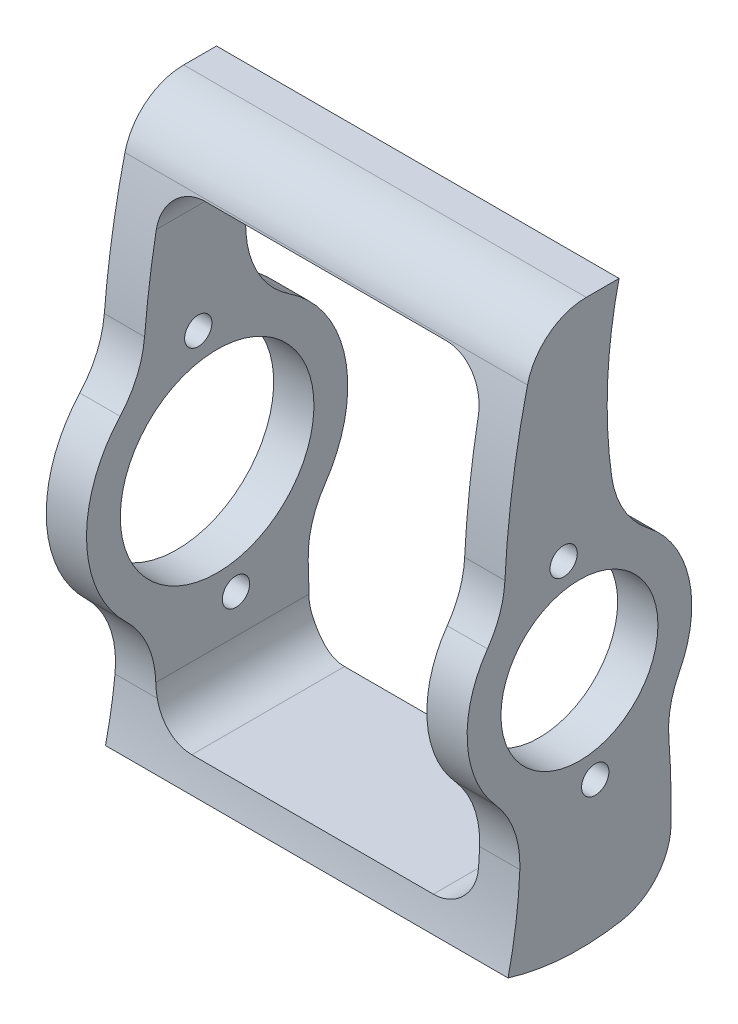
SolidWorks part; units mm, degrees
other "Markup2"
sketch "Sketch9" plane through (31.75, 50.4016, 20.35) normal (0.8402, 0.4575, 0.2911) x (0.3274, 0, -0.9449)
material "AISI 4340 Steel, normalized"
ref_plane "Front Plane" through (0, 0, 0) normal (0, 0, 1) x (1, 0, 0)
ref_plane "Top Plane" through (0, 0, 0) normal (0, 1, 0) x (1, 0, 0)
ref_plane "Right Plane" through (0, 0, 0) normal (1, 0, 0) x (0, 0, -1)
other "Center of Mass"
sketch "Weapon Layout" plane through (0, 0, 0) normal (1, 0, 0) x (0, 0, -1)
  line L0 (-6.2484, 50.4143) -> (6.2484, 50.4143) construction
  line L1 (-11.2609, -36.3978) -> (14.119, -35.3873) construction
  line L2 (6.2484, 50.4143) -> (-5.4512, 0) construction
  line L3 (6.2484, 50.4143) -> (0, 0) construction
  line L4 (0, 0) -> (0, -35.9495) construction
  circle A0 centre (0, 0) radius 14 construction
  circle A1 centre (0, 0) radius 50.8 construction
  circle A2 centre (0, 0) radius 17.175 construction
  circle A3 centre (0, 0) radius 20.35 construction
  arc A4 (-6.2484, 50.4143) -> (-20.35, 0) centre (76.8181, 0) ccw construction
  arc A5 (25.0504, -28.707) -> (-25.4024, -28.3959) centre (0, 0) cw construction
  arc A6 (6.2484, 50.4143) -> (15.4079, 13.2936) centre (47.3713, 40.8709) ccw construction
  dimension "D1" = 28
  dimension "D2" = 101.6
  dimension "D3" = 3.175
  dimension "D4" = 6.35
  dimension "D5" = 12.4968
  dimension "D7" = 6
  dimension "D6" = 12.7
  dimension "D8" = 25.4
  dimension "D9" = 87.72
sketch "Sketch2" plane through (0, 0, 0) normal (1, 0, 0) x (0, 0, -1)
  line L0 (-6.2484, 50.4143) -> (6.2484, 50.4143)
  line L1 (-11.3224, -1.5644) -> (0, 0) construction
  line L2 (6.2484, 50.4143) -> (-5.4512, 0) construction
  line L3 (-11.5831, 0.9204) -> (-15.1384, 50.4143) construction
  arc A0 (-11.2609, -36.3978) -> (14.119, -35.3873) centre (0, 0) ccw
  arc A1 (-25.4024, -28.3959) -> (25.0504, -28.707) centre (0, 0) ccw construction
  arc A2 (-10.8995, -4.0268) -> (-11.5831, 0.9204) centre (26.419, 3.6503) cw
  arc A3 (9.7624, 6.6179) -> (11.7942, -0.0229) centre (-25.5032, -7.8024) cw
  arc A4 (-11.5831, 0.9204) -> (-6.2484, 50.4143) centre (127.7924, 10.9323) cw
  arc A5 (-10.8995, -4.0268) -> (-11.2609, -36.3978) centre (-85.5365, -19.3811) cw
  arc A6 (6.2484, 50.4143) -> (9.7624, 6.6179) centre (76.8178, 34.0373) ccw
  arc A7 (11.7942, -0.0229) -> (14.119, -35.3873) centre (-112.5302, -25.9546) cw
  circle A9 centre (0, 0) radius 11.43 construction
  point P25 (10.9299, 3.3439)
  dimension "D1" = 127
  dimension "D2" = 38.1
  dimension "D3" = 76.2
  dimension "D4" = 38.1
  dimension "D5" = 22.86
  dimension "D6" = 8.89
extrude "Boss-Extrude2" add sketch "Sketch2" along normal mid plane 63.5
sketch "Sketch3" plane through (0, 0, 0) normal (0, 0, 1) x (1, 0, 0)
  line L0 (31.75, 50.4143) -> (-31.75, 50.4143) construction
  line L1 (-25.4, 42.7943) -> (25.4, 42.7943)
  line L2 (-25.4, 42.7943) -> (-25.4, -31.75)
  line L3 (-25.4, -31.75) -> (25.4, -31.75)
  line L4 (25.4, 42.7943) -> (25.4, -31.75)
  line L6 (-31.75, -38.1) -> (31.75, -38.1) construction
  line L7 (-31.75, 50.4143) -> (-31.75, 0.9204) construction
  dimension "D4" = 6.35
  dimension "D1" = 7.62
  dimension "D3" = 6.35
  dimension "D2" = 6.35
extrude "Cut-Extrude1" cut sketch "Sketch3" against normal through all both and the other way through all
fillet "Fillet1" radius 6.35 4 edges at (-25.4, 42.7943, 1.6785) (25.4, 42.7943, 1.6785) (25.4, -31.75, -1.9952) (-25.4, -31.75, -1.9952)
fillet "Fillet3" radius 9.525 2 edges at (0, -35.3873, -14.119) (0, 50.4143, 6.2484)
sketch "Sketch6" plane through (-31.75, 0, 0) normal (-1, 0, 0) x (0, 0, 1)
  circle A0 centre (0, 0) radius 20.604
  dimension "D1" = 41.208
extrude "Boss-Extrude3" add sketch "Sketch6" against normal up to surface (6.35 mm away) up to face at (-25.4, 3.1884, 0.3076)
sketch "Sketch7" plane through (-31.75, 0, 0) normal (-1, 0, 0) x (0, 0, 1)
  circle A0 centre (0, 0) radius 15.27
  arc A1 (9.3433, -18.3637) -> (11.8156, 16.8795) centre (0, 0) ccw construction
  dimension "D1" = 30.54
extrude "Cut-Extrude3" cut sketch "Sketch7" against normal up to next
sketch "Sketch10" plane through (31.75, 0, 0) normal (1, 0, 0) x (0, 0, -1)
  circle A0 centre (0, 0) radius 17.7165
  dimension "D1" = 35.433
extrude "Boss-Extrude4" add sketch "Sketch10" against normal up to surface (6.35 mm away) up to face at (25.4, 3.1884, 0.3076)
sketch "Sketch5" plane through (31.75, 0, 0) normal (1, 0, 0) x (0, 0, -1)
  circle A0 centre (0, 0) radius 12.3825
  circle A1 centre (0, 0) radius 6.35 construction
  dimension "D1" = 12.7
  dimension "D2" = 24.765
extrude "Cut-Extrude2" cut sketch "Sketch5" against normal up to next
fillet "Fillet2" radius 15.24 8 edges at (-28.575, 16.8795, 11.8156) (-28.575, -18.3637, 9.3433) (-28.575, -15.1114, -14.006) (-28.575, 19.7734, -5.7912) (28.575, 16.4667, -6.5361) (28.575, -11.3248, -13.6243) (28.575, -14.9769, 9.4639) (28.575, 13.1019, 11.9254)
sketch "Sketch11" plane through (31.75, 0, 0) normal (1, 0, 0) x (0, 0, -1)
  circle A0 centre (-2.4917, 16.1603) radius 1.8986
  circle A1 centre (-2.4917, 16.1603) radius 1.8986 construction
  circle A2 centre (2.4917, -16.1603) radius 1.8987
  circle A3 centre (2.4917, -16.1603) radius 1.8986 construction
hole_wizard "#6 Clearance Hole1" positions "Sketch12" profile "Sketch13" hole size "#6" standard "ANSI Inch"
sketch "Sketch12" plane through (-31.75, 0, 0) normal (1, 0, 0) x (0, 0, -1)
  point P0 (-2.9763, 19.3027)
  point P3 (2.9763, -19.3027)
sketch "Sketch13" plane through (-31.75, 19.3027, 2.9763) normal (0, 1, 0) x (0, 0, 1)
  line L0 (0, 0) -> (0, 8.9134)
  line L1 (0, 8.9134) -> (2.1526, 7.62)
  line L2 (2.1526, 7.62) -> (2.1526, 0)
  line L5 (2.1526, 0) -> (0, 0)
  line L10 (0, 8.9134) -> (-2.1527, 7.62) construction
  line L11 (0, -6.35) -> (0, 107.95) construction
  dimension "Hole Dia." = 4.3053
  dimension "Hole Depth" = 7.62
  dimension "Drill Angle" = 118
hole_wizard "#6 Clearance Hole2" positions "Sketch14" profile "Sketch16" hole size "#6" standard "ANSI Inch" end condition up to next
sketch "Sketch14" plane through (31.75, 0, 0) normal (1, 0, 0) x (0, 0, -1)
  point P0 (-2.4917, 16.1603)
  point P3 (2.4917, -16.1603)
sketch "Sketch16" plane through (31.75, 16.1603, 2.4917) normal (0, 1, 0) x (0, 0, -1)
  line L0 (0, 0) -> (0, 6.35)
  line L1 (0, 6.35) -> (2.1526, 6.35)
  line L2 (2.1526, 6.35) -> (2.1526, 0)
  line L5 (2.1526, 0) -> (0, 0)
  line L11 (0, -6.35) -> (0, 107.95) construction
  dimension "Thru Hole Dia." = 4.3053
  dimension "Thru Hole Depth" = 6.35
other "Center of Mass Reference Point1"
equation "\"D1@Weapon Layout\" = 28mm"
equation "\"D1@Sketch6\"=\"bearing OD L\"+.42in+0.1in"
equation "\"D2@Sketch3\"=\"D3@Sketch3\""
equation "\"D1@Sketch7\"=\"bearing OD L\"+0.1in"
equation "\"D2@Sketch5\"=\"bearing OD R\" + .1"
equation "\"D1@Sketch10\"=\"bearing OD R\" + 0.42 + .1"
equation "\"bearing OD R\"= 7 / 8"
equation "\"bearing OD L\"= 28mm"
